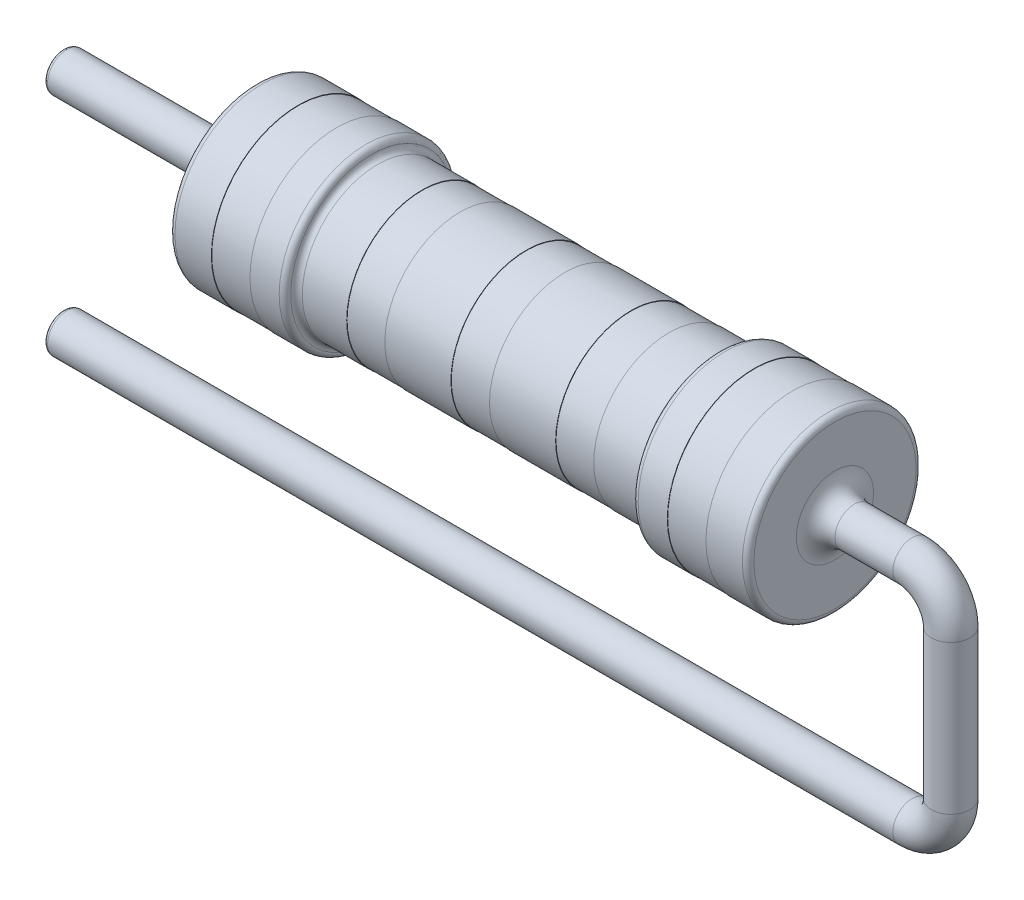
SolidWorks part; units mm, degrees
ref_plane "Front Plane" through (0, 0, 0) normal (0, 0, 1) x (1, 0, 0)
ref_plane "Top Plane" through (0, 0, 0) normal (0, 1, 0) x (1, 0, 0)
ref_plane "Right Plane" through (0, 0, 0) normal (1, 0, 0) x (0, 0, -1)
sketch "Sketch1" plane through (0, 0, 0) normal (0, 0, 1) x (1, 0, 0)
  line L0 (-7.5, -1.8974) -> (7.5, -1.8974)
  line L1 (7.5, -1.8974) -> (7.5, -4.1474)
  line L2 (7.5, -4.1474) -> (6.4068, -4.1474)
  line L3 (-7.5, -1.8974) -> (-7.5, -4.1474)
  line L4 (6.4068, -4.1474) -> (6.4068, -4.1374)
  line L5 (6.4068, -4.1374) -> (5.4068, -4.1374)
  line L6 (5.4068, -4.1374) -> (5.4068, -4.1474)
  line L7 (5.4068, -4.1474) -> (4.5, -4.1474)
  line L8 (4.5, -4.1474) -> (4.5, -3.8474)
  line L9 (4.5, -3.8474) -> (3.2, -3.8474)
  line L10 (3.2, -3.8474) -> (3.2, -3.8374)
  line L11 (3.2, -3.8374) -> (2.2127, -3.8374)
  line L12 (2.2127, -3.8374) -> (2.2127, -3.8474)
  line L13 (2.2127, -3.8474) -> (0.5, -3.8474)
  line L14 (0.5, -3.8474) -> (0.5, -3.8374)
  line L15 (0.5, -3.8374) -> (-0.5, -3.8374)
  line L16 (-0.5, -3.8474) -> (-0.5, -3.8374)
  line L17 (-2.2127, -3.8474) -> (-0.5, -3.8474)
  line L18 (-2.2127, -3.8374) -> (-2.2127, -3.8474)
  line L19 (-3.2, -3.8374) -> (-2.2127, -3.8374)
  line L20 (-3.2, -3.8474) -> (-3.2, -3.8374)
  line L21 (-4.5, -3.8474) -> (-3.2, -3.8474)
  line L22 (-4.5, -4.1474) -> (-4.5, -3.8474)
  line L23 (-5.4068, -4.1474) -> (-4.5, -4.1474)
  line L24 (-5.4068, -4.1374) -> (-5.4068, -4.1474)
  line L25 (-6.4068, -4.1374) -> (-5.4068, -4.1374)
  line L26 (-6.4068, -4.1474) -> (-6.4068, -4.1374)
  line L27 (-7.5, -4.1474) -> (-6.4068, -4.1474)
  line L28 (-7.5, -4.1474) -> (-7.5091, -4.1346)
  dimension "D2" = 3
  dimension "D3" = 1
  dimension "D4" = 2.25
  dimension "D5" = 0.01
  dimension "D7" = 0.01
  dimension "D8" = 0.3
  dimension "D9" = 0.01
  dimension "D10" = 0.01
revolve "Revolve2" add sketch "Sketch1" angle 360 about L0
sketch "Sketch3" plane through (7.5, 0, 0) normal (1, 0, 0) x (0, 0, -1)
  circle A0 centre (0, -1.8974) radius 0.5
sketch3d "3DSketch1"
  line L0 (7.5, -1.8974, 0) -> (9.5, -1.8974, 0)
  line L1 (10.5, -2.8974, 0) -> (10.5, -6.754, 0)
  line L2 (9.5, -7.754, 0) -> (-12.5, -7.754, 0)
  arc A0 (10.5, -2.8974, 0) -> (9.5, -1.8974, 0) centre (9.5, -2.8974, 0) ccw
  arc A1 (9.5, -7.754, 0) -> (10.5, -6.754, 0) centre (9.5, -6.754, 0) ccw
  point P6 (10.5, -1.8974, 0)
  point P7 (9.5, -2.8974, 1)
  point P11 (10.5, -7.754, 0)
  point P12 (9.5, -6.754, 1)
  dimension "D3" = 1
  dimension "D4" = 1
  dimension "D1" = 3
  dimension "D2" = 23
fillet "Fillet2" radius 0.15 4 edges at (4.5, -1.8974, 2.25) (-4.5, -1.8974, 2.25) (-7.5, -1.8974, 2.25) (7.5, -1.8974, 2.25)
fillet "Fillet3" radius 0.15 2 edges at (4.5, -1.8974, 1.95) (-4.5, -1.8974, 1.95)
sweep "Sweep2" add profiles "Sketch3" path "3DSketch1"
sketch "Sketch5" plane through (-7.5, 0, 0) normal (-1, 0, 0) x (0, 0, 1)
  circle A0 centre (0, -1.8974) radius 0.5
sketch3d "3DSketch5"
  line L0 (-7.5, -1.8974, 0) -> (-12.5, -1.8974, 0)
  dimension "D1" = 5
sweep "Sweep3" add profiles "Sketch5" path "3DSketch5"
fillet "Fillet4" radius 0.1 2 edges at (-12.5, -7.754, -0.5) (-12.5, -1.8974, 0.5)
fillet "Fillet5" radius 0.5 2 edges at (7.5, -1.8974, -0.5) (-7.5, -1.8974, 0.5)
